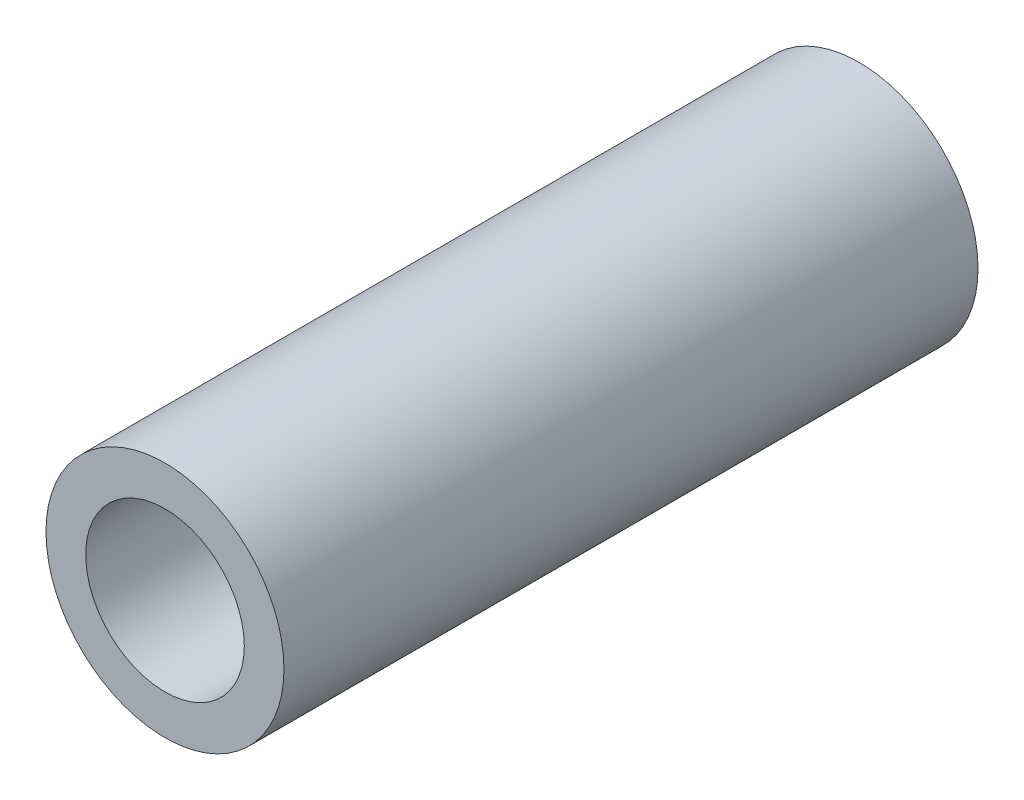
SolidWorks part; units mm, degrees
ref_plane "Front Plane" through (0, 0, 0) normal (0, 0, 1) x (1, 0, 0)
ref_plane "Top Plane" through (0, 0, 0) normal (0, 1, 0) x (1, 0, 0)
ref_plane "Right Plane" through (0, 0, 0) normal (1, 0, 0) x (0, 0, -1)
sketch "Sketch1" plane through (0, 0, 0) normal (0, 0, 1) x (1, 0, 0)
  circle A0 centre (0, 0) radius 6
  circle A1 centre (0, 0) radius 4
  dimension "D1" = 12
  dimension "D2" = 8
extrude "Boss-Extrude1" add sketch "Sketch1" along normal blind 33
extrude "Boss-Extrude2" add sketch "Sketch1<2>" against normal blind 2 contours A1 | A0 A1 region at (-5.8303, 0, 0) region at (0, 0, 0)
sketch "Sketch1<2>" plane through (0, 0, 0) normal (0, 0, 1) x (1, 0, 0) same geometry as "Sketch1"
